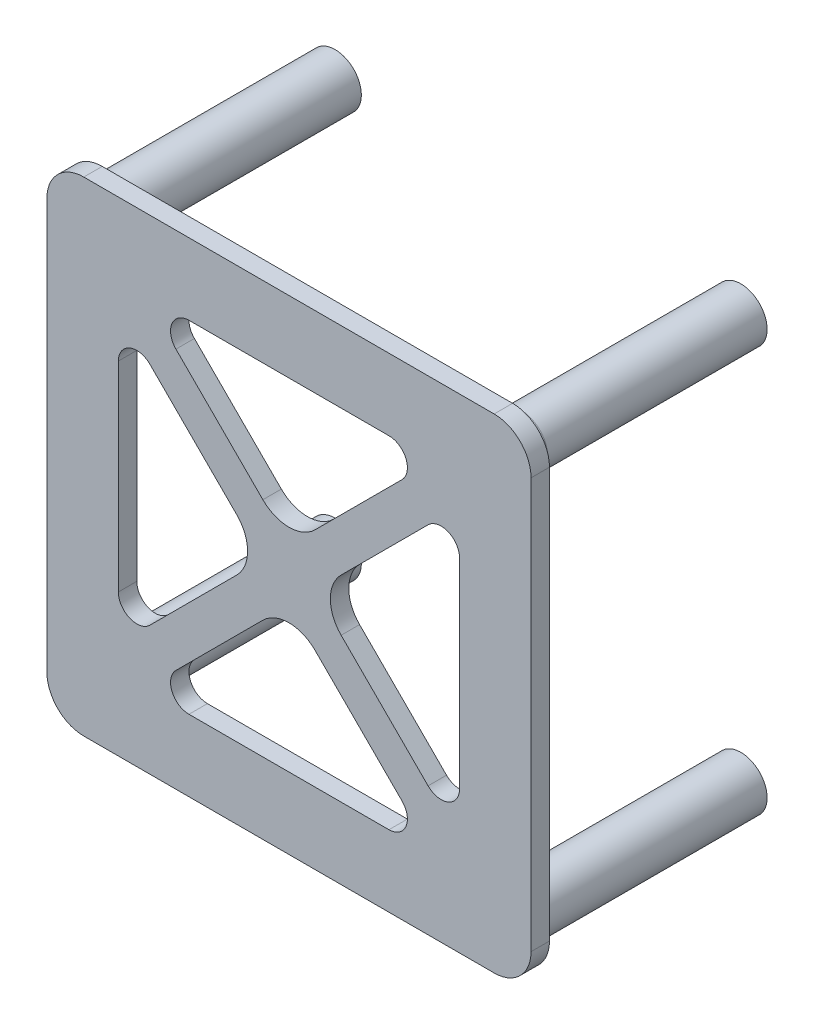
SolidWorks part; units mm, degrees
ref_plane "Front Plane" through (0, 0, 0) normal (0, 0, 1) x (1, 0, 0)
ref_plane "Top Plane" through (0, 0, 0) normal (0, 1, 0) x (1, 0, 0)
ref_plane "Right Plane" through (0, 0, 0) normal (1, 0, 0) x (0, 0, -1)
sketch "Sketch1" plane through (0, 0, 0) normal (0, 0, 1) x (1, 0, 0)
  line L0 (-35.6221, 10.9987) -> (8.3779, -33.0013) construction
  line L1 (-35.6221, -33.0013) -> (8.3779, 10.9987) construction
  line L2 (-32.1221, 4.6703) -> (-16.4505, -11.0013)
  line L3 (-39.8721, 15.2487) -> (12.6279, 15.2487)
  line L4 (-39.8721, 15.2487) -> (-39.8721, -37.2513)
  line L5 (-39.8721, -37.2513) -> (12.6279, -37.2513)
  line L6 (12.6279, 15.2487) -> (12.6279, -37.2513)
  line L7 (-39.8721, 15.2487) -> (12.6279, -37.2513) construction
  line L8 (-39.8721, -37.2513) -> (12.6279, 15.2487) construction
  line L9 (-29.2936, 7.4987) -> (2.0495, 7.4987)
  line L10 (-32.1221, 4.6703) -> (-32.1221, -26.6729)
  line L11 (-29.2936, -29.5013) -> (2.0495, -29.5013)
  line L12 (4.8779, 4.6703) -> (4.8779, -26.6729)
  line L13 (-32.1221, 7.4987) -> (4.8779, -29.5013) construction
  line L14 (-32.1221, -29.5013) -> (4.8779, 7.4987) construction
  line L15 (-29.2936, 7.4987) -> (-13.6221, -8.1729)
  line L16 (-32.1221, -26.6729) -> (-16.4505, -11.0013)
  line L17 (4.8779, 4.6703) -> (-10.7936, -11.0013)
  line L18 (-13.6221, -8.1729) -> (2.0495, 7.4987)
  line L19 (-13.6221, -13.8297) -> (-29.2936, -29.5013)
  line L20 (-13.6221, -13.8297) -> (2.0495, -29.5013)
  line L21 (-10.7936, -11.0013) -> (4.8779, -26.6729)
  circle A0 centre (-35.6221, 10.9987) radius 1.25
  circle A1 centre (-35.6221, 10.9987) radius 2.85
  circle A2 centre (8.3779, 10.9987) radius 1.25
  circle A3 centre (8.3779, 10.9987) radius 2.85
  circle A4 centre (-35.6221, -33.0013) radius 1.25
  circle A5 centre (-35.6221, -33.0013) radius 2.85
  circle A6 centre (8.3779, -33.0013) radius 1.25
  circle A7 centre (8.3779, -33.0013) radius 2.85
  point P12 (-13.6221, -11.0013)
  point P17 (-13.6221, -11.0013)
  dimension "D3" = 2.5
  dimension "D4" = 2.5
  dimension "D5" = 2.5
  dimension "D6" = 2.5
  dimension "D7" = 1.6
  dimension "D8" = 1.6
  dimension "D9" = 1.6
  dimension "D10" = 1.6
  dimension "D1" = 44
  dimension "D2" = 44
  dimension "D11" = 52.5
  dimension "D12" = 52.5
  dimension "D13" = 37
  dimension "D14" = 2
  dimension "D15" = 2
  dimension "D16" = 2
  dimension "D17" = 2
extrude "Boss-Extrude1" add sketch "Sketch1" along normal blind 2 contours L6 L3 L4 L5 A7 A5 A3 A1 | A5 A4 | A7 A6 | A6 | A3 A2 | A2 | A1 A0 | A0 | A4 region at (-13.6221, -11.0013, 0) region at (-35.6221, 10.9987, 0) region at (-38.3915, 10.9987, 0) region at (8.3779, 10.9987, 0) region at (5.6085, 10.9987, 0) region at (-38.3915, -33.0013, 0) region at (8.3779, -33.0013, 0) region at (5.6085, -33.0013, 0)
extrude "Boss-Extrude2" add sketch "Sketch1<3>" against normal blind 25 contours A1 A0 | A5 A4 | A7 A6 | A3 A2 region at (-38.3915, 10.9987, 0) region at (5.6085, 10.9987, 0) region at (-38.3915, -33.0013, 0) region at (5.6085, -33.0013, 0)
sketch "Sketch1<3>" plane through (0, 0, 0) normal (0, 0, 1) x (1, 0, 0) same geometry as "Sketch1"
fillet "Fillet1" radius 4 4 edges at (-39.8721, 15.2487, 1) (12.6279, -37.2513, 1) (12.6279, 15.2487, 1) (-39.8721, -37.2513, 1)
fillet "Fillet2" radius 1.2 4 edges at (11.2279, -33.0013, 0) (-32.7721, -33.0013, 0) (-32.7721, 10.9987, 0) (11.2279, 10.9987, 0)
fillet "Fillet3" radius 2 8 edges at (-29.2936, 7.4987, 1) (2.0495, 7.4987, 1) (4.8779, 4.6703, 1) (4.8779, -26.6729, 1) (2.0495, -29.5013, 1) (-29.2936, -29.5013, 1) (-32.1221, -26.6729, 1) (-32.1221, 4.6703, 1)
fillet "Fillet4" radius 4 4 edges at (-13.6221, -8.1729, 1) (-16.4505, -11.0013, 1) (-13.6221, -13.8297, 1) (-10.7936, -11.0013, 1)
equation "\"D8@Sketch1\"=\"D7@Sketch1\""
equation "\"D9@Sketch1\"=\"D7@Sketch1\""
equation "\"D10@Sketch1\"=\"D7@Sketch1\""
